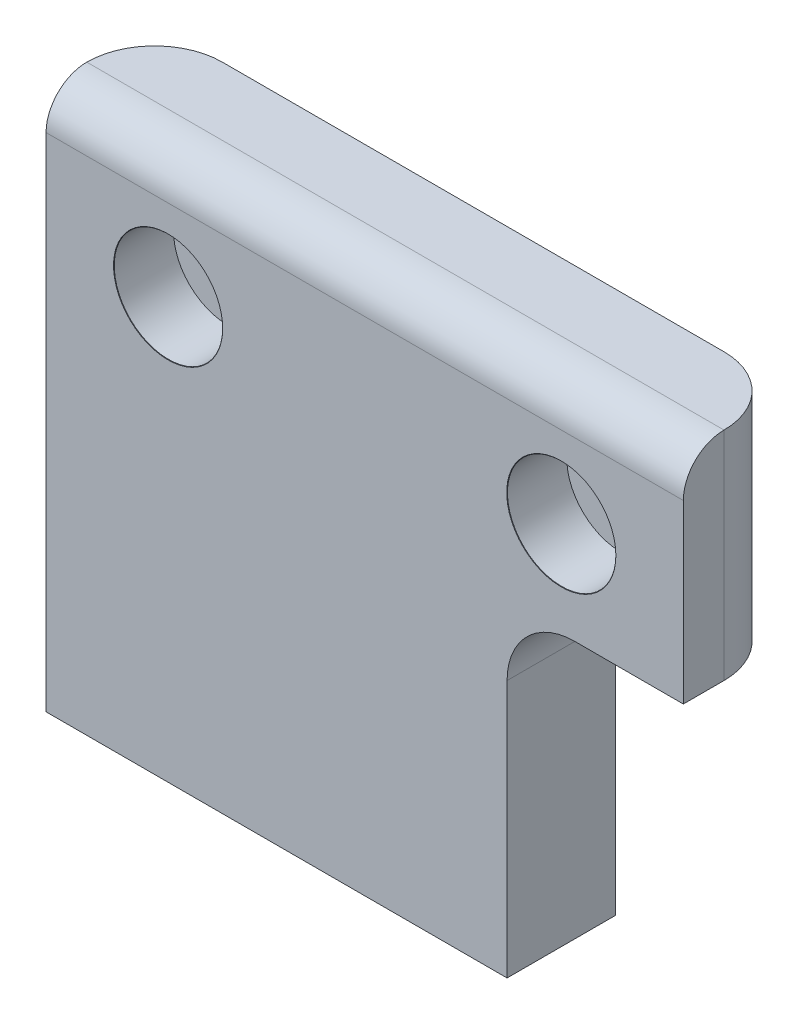
SolidWorks part; units mm, degrees
material "K110"
ref_plane "Front Plane" through (0, 0, 0) normal (0, 0, 1) x (1, 0, 0)
ref_plane "Top Plane" through (0, 0, 0) normal (0, 1, 0) x (1, 0, 0)
ref_plane "Right Plane" through (0, 0, 0) normal (1, 0, 0) x (0, 0, -1)
sketch "Sketch1" plane through (0, 0, 0) normal (0, 1, 0) x (1, 0, 0)
  line L1 (-23.5, -4) -> (23.5, -4)
  line L2 (-23.5, -4) -> (-23.5, 4)
  line L3 (-23.5, 4) -> (23.5, 4)
  line L4 (23.5, -4) -> (23.5, 4)
  line L5 (-23.5, -4) -> (23.5, 4) construction
  line L6 (-23.5, 4) -> (23.5, -4) construction
  point P0 (0, 0)
  dimension "D1" = 8
  dimension "D2" = 47
extrude "Boss-Extrude1" add sketch "Sketch1" against normal blind 40
fillet "Fillet1" radius 3 1 edges at (0, 0, 4)
fillet "Fillet2" radius 5 2 edges at (-23.5, -20, -4) (23.5, -20, -4)
hole_wizard "CBORE for M4 Hex Socket Head Cap Screw1" positions "Sketch6" profile "Sketch3" counterbore size "M4" standard "ISO" end condition through all
sketch "Sketch6" plane through (0, 0, 4) normal (0, 0, 1) x (1, 0, 0)
  line L1 (23.5, -3) -> (-23.5, -3) construction
  line L2 (-23.5, -40) -> (-23.5, -3) construction
  line L3 (23.5, -40) -> (23.5, -3) construction
  point P0 (-14.5, -9)
  point P2 (14.5, -9)
  dimension "D1" = 6
  dimension "D2" = 9
  dimension "D3" = 9
sketch "Sketch3" plane through (-14.5, -9, 4) normal (1, 0, 0) x (0, -1, 0)
  line L0 (0, 0) -> (0, 8)
  line L1 (0, 8) -> (2.15, 8)
  line L3 (2.15, 8) -> (2.15, 4.4)
  line L4 (4, 4.4) -> (2.15, 4.4)
  line L5 (4, 4.4) -> (4, 0.025)
  line L6 (4, 0.025) -> (4.025, 0)
  line L7 (4.025, 0) -> (0, 0)
  line L8 (-4, 0.025) -> (-4.025, 0) construction
  line L11 (0, -6.35) -> (0, 107.95) construction
  dimension "Thru Hole Dia." = 4.3
  dimension "Thru Hole Depth" = 8
  dimension "C'Bore Dia." = 8
  dimension "C'Bore Depth" = 4.4
  dimension "Near C'Sink Dia." = 8.05
  dimension "Near C'Sink Angle" = 90
sketch "Sketch5" plane through (0, 0, 4) normal (0, 0, 1) x (1, 0, 0)
  line L0 (23.5, -40) -> (23.5, -3) construction
  line L1 (23.5, -40) -> (10.5, -40)
  line L2 (23.5, -40) -> (23.5, -16.0022)
  line L3 (23.5, -16.0022) -> (10.5, -16.0022)
  line L4 (10.5, -40) -> (10.5, -16.0022)
  line L6 (19.4978, -28.0022) -> (29.5, -28.0022) construction
  dimension "D1" = 12
  dimension "D2" = 13
extrude "Cut-Extrude1" cut sketch "Sketch5" against normal up to next
fillet "Fillet3" radius 5 1 edges at (10.5, -16.0022, 0)
